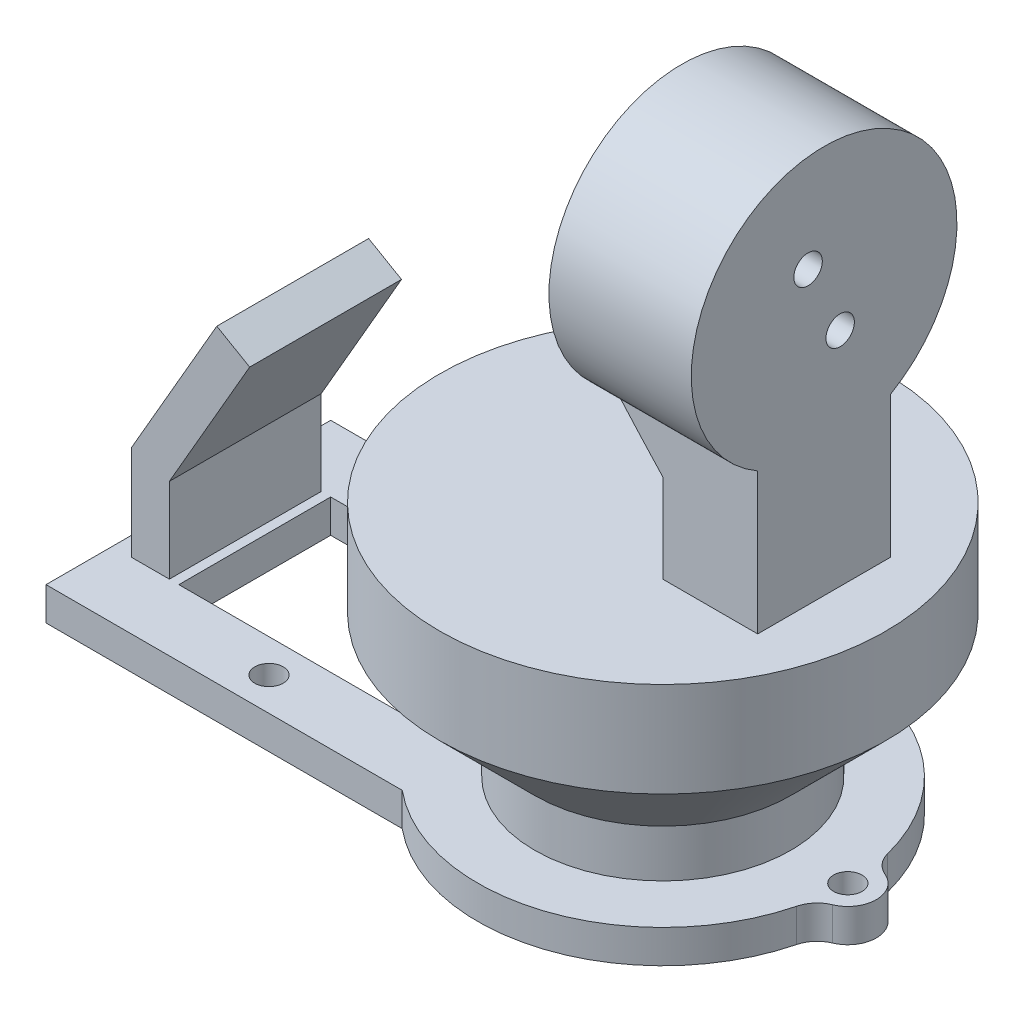
SolidWorks part; units mm, degrees
ref_plane "Front" through (0, 0, 0) normal (0, 0, 1) x (1, 0, 0)
ref_plane "Top" through (0, 0, 0) normal (0, 1, 0) x (1, 0, 0)
ref_plane "Right" through (0, 0, 0) normal (1, 0, 0) x (0, 0, -1)
sketch "Sketch1" plane through (0, 0, 0) normal (0, 1, 0) x (1, 0, 0)
  line L0 (-12.4599, 15) -> (-50, 15)
  line L1 (-50, 15) -> (-50, -15)
  line L2 (-50, -15) -> (-12.4599, -15)
  line L3 (-12.4599, 8) -> (-43, 8)
  line L4 (-43, 8) -> (-43, -8)
  line L5 (-43, -8) -> (-12.4599, -8)
  circle A0 centre (0, 0) radius 13.5
  arc A1 (19.4423, -1.4989) -> (19.4423, 1.4989) centre (0, 0) ccw
  arc A2 (20.6538, -2.7692) -> (20.6538, 2.7692) centre (19.5, 0) ccw
  circle A3 centre (19.5, 0) radius 1.5
  circle A4 centre (0, 0) radius 19.5 construction
  arc A5 (18.9, 4.8) -> (18.9, -4.8) centre (0, 0) ccw
  arc A6 (20.6538, -2.7692) -> (18.9, -4.8) centre (21.8077, -5.5385) ccw
  arc A7 (18.9, 4.8) -> (20.6538, 2.7692) centre (21.8077, 5.5385) ccw
  circle A8 centre (-30, 11.5) radius 1.5
  circle A9 centre (-30, -11.5) radius 1.5
  point P19 (19.2692, 2.9911)
  dimension "D1" = 27
  dimension "D4" = 6
  dimension "D5" = 3
  dimension "D6" = 3
  dimension "D10" = 3
  dimension "D11" = 3
  dimension "D3" = 50
  dimension "D7" = 15
  dimension "D8" = 15
  dimension "D12" = 3.5
  dimension "D13" = 3.5
  dimension "D14" = 30
  dimension "D2" = 6
  dimension "D9" = 7
extrude "Boss-Extrude1" add sketch "Sketch1" along normal blind 3.5 contours A5 L0 L1 L2 L5 L4 L3 A9 A8 | A7 A5 A6 A2 A3 A0 | A0 region at (-15.9039, 0, -12.0949) region at (5.8542, 0, -17.9987) region at (0, 0, 0)
sketch "Sketch2" plane through (0, 0, -8) normal (0, 0, 1) x (1, 0, 0)
  line L0 (-48, 3.5) -> (-48, 13.5)
  line L1 (-50, 3.5) -> (-12.4599, 3.5) construction
  line L2 (-48, 13.5) -> (-39, 29.0885)
  line L3 (-39, 29.0885) -> (-35.5359, 27.0885)
  line L4 (-35.5359, 27.0885) -> (-44, 12.4282)
  line L5 (-44, 3.5) -> (-44, 13.5) construction
  line L6 (-44, 3.5) -> (-44, 12.4282)
  line L7 (-50, 3.5) -> (-50, 0) construction
  line L8 (-48, 3.5) -> (-44, 3.5)
  dimension "D1" = 4
  dimension "D2" = 4
  dimension "D3" = 2
  dimension "D4" = 10
  dimension "D5" = 18
  dimension "D6" = 150
extrude "Boss-Extrude2" add sketch "Sketch2" along normal blind 16 contours L2 L3 L4 L6 L8 L0
sketch "Sketch4" plane through (0, 3.5, 0) normal (0, 1, 0) x (1, 0, 0)
  circle A0 centre (0, 0) radius 13.5
  dimension "D1" = 27
extrude "Boss-Extrude3" add sketch "Sketch4" along normal blind 15
sketch "Sketch5" plane through (0, 18.5, 0) normal (0, 1, 0) x (1, 0, 0)
  circle A0 centre (0, 0) radius 23.5
  dimension "D1" = 47
extrude "Boss-Extrude4" add sketch "Sketch5" along normal blind 10
sketch "Sketch6" plane through (0, 28.5, 0) normal (0, 1, 0) x (1, 0, 0)
  line L1 (7, -7) -> (17, -7)
  line L2 (7, -7) -> (7, 7)
  line L3 (7, 7) -> (17, 7)
  line L4 (17, -7) -> (17, 7)
  line L5 (7, -7) -> (17, 7) construction
  line L6 (7, 7) -> (17, -7) construction
  point P0 (12, 0)
  dimension "D1" = 10
  dimension "D2" = 14
  dimension "D3" = 12
extrude "Boss-Extrude5" add sketch "Sketch6" along normal blind 20
sketch "Sketch7" plane through (17, 0, 0) normal (1, 0, 0) x (0, 0, -1)
  line L0 (-7, 48.5) -> (7, 48.5) construction
  circle A0 centre (0, 55.5) radius 14
  dimension "D1" = 28
  dimension "D2" = 7
extrude "Boss-Extrude6" add sketch "Sketch7" against normal blind 15
sketch "Sketch8" plane through (0, 0, 0) normal (0, 0, 1) x (1, 0, 0)
  line L0 (2, 41.5) -> (7, 41.5) construction
  line L1 (17, 69.5) -> (2, 69.5) construction
  line L2 (2, 41.5) -> (7, 41.5) construction
  line L3 (17, 69.5) -> (2, 69.5)
  line L4 (14, 69.5) -> (17, 43.3756)
  line L5 (2, 41.5) -> (8, 69.5)
  line L6 (2, 41.5) -> (2, 69.5)
  line L7 (17, 69.5) -> (17, 43.3756)
  dimension "D1" = 6
  dimension "D2" = 3
extrude "Cut-Extrude2" [suppressed] cut sketch "Sketch8" against normal mid plane 30 contours L6 L5 L3 | L7 L3 L4
chamfer "Chamfer1" distance 10 angle 45 1 edges at (0, 18.5, 13.5)
sketch "Sketch9" [suppressed] plane through (7, 0, 0) normal (-1, 0, 0) x (0, 0, 1)
  circle A0 centre (0, 61.5) radius 14 construction
  circle A1 centre (0, 61.5) radius 14
  circle A2 centre (0, 61.5) radius 12
  dimension "D1" = 2
extrude "Cut-Extrude3" [suppressed] cut sketch "Sketch9" along normal blind 30 and the other way blind 1 contours A2
sketch "Sketch10" plane through (2, 0, 0) normal (-1, 0, 0) x (0, 0, 1)
  line L0 (-14, 55.5) -> (14, 55.5) construction
  line L1 (-1.6905, 51.8748) -> (1.6905, 59.1252) construction
  circle A3 centre (1.6905, 59.1252) radius 1.5
  circle A4 centre (-1.6905, 51.8748) radius 1.5
  circle A5 centre (0, 55.5) radius 14 construction
  point P14 (0, 55.5)
  dimension "D1" = 65
  dimension "D2" = 3
  dimension "D3" = 3
  dimension "D4" = 8
extrude "Cut-Extrude4" cut sketch "Sketch10" against normal up to next
chamfer "Chamfer2" distance 5 angle 45 1 edges at (7, 41.5, 0)
